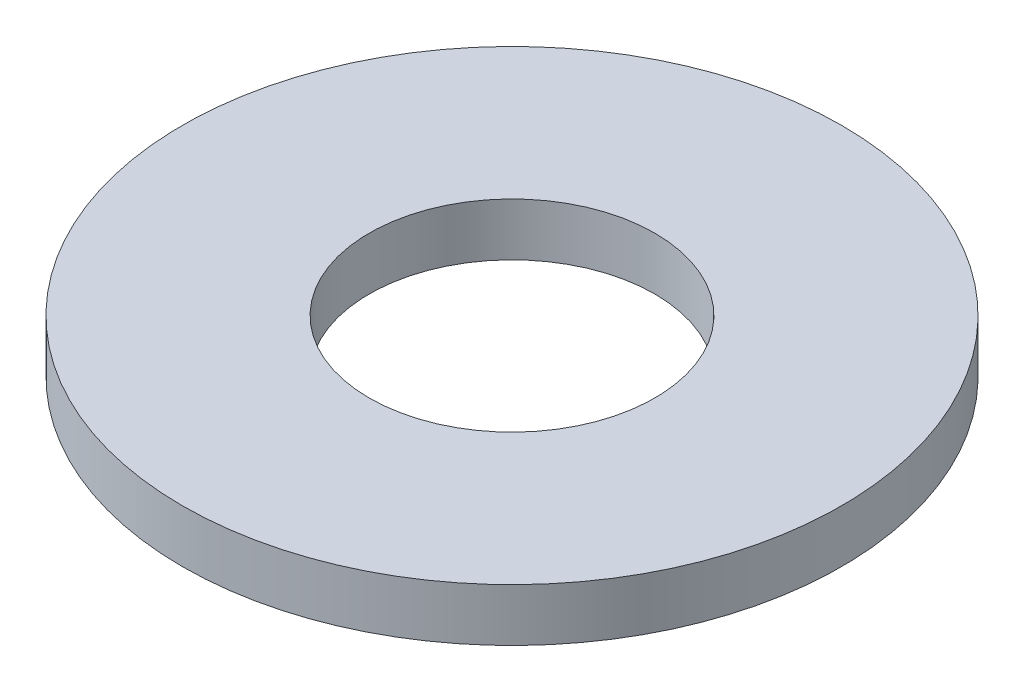
SolidWorks part; units mm, degrees
ref_plane "Front Plane" through (0, 0, 0) normal (0, 0, 1) x (1, 0, 0)
ref_plane "Top Plane" through (0, 0, 0) normal (0, 1, 0) x (1, 0, 0)
ref_plane "Right Plane" through (0, 0, 0) normal (1, 0, 0) x (0, 0, -1)
sketch "Sketch1" plane through (0, 0, 0) normal (0, 1, 0) x (1, 0, 0)
  circle A0 centre (0, 0) radius 75
  dimension "FLANGE_OD" = 150
extrude "Boss-Extrude1" add sketch "Sketch1" along normal blind 12
sketch "Sketch2" plane through (0, 0, 0) normal (0, 1, 0) x (1, 0, 0)
  circle A0 centre (0, 0) radius 32.5
  dimension "BORE_D" = 65
extrude "Cut-Extrude1" cut sketch "Sketch2" along normal through all
sketch "Sketch3" plane through (0, 12, 0) normal (0, 1, 0) x (1, 0, 0)
  circle A0 centre (0, 0) radius 27.8193 construction
  circle A1 centre (-27.8193, 0) radius 3.5338
  dimension "BOLT_D" = 7.0676
  dimension "BOLT_PCD" = 55.6385
extrude "Cut-Extrude2" cut sketch "Sketch3" against normal blind 9.9723 rebuild error yes
pattern_circular "CirPattern1" count 5 over 360 rebuild error yes
